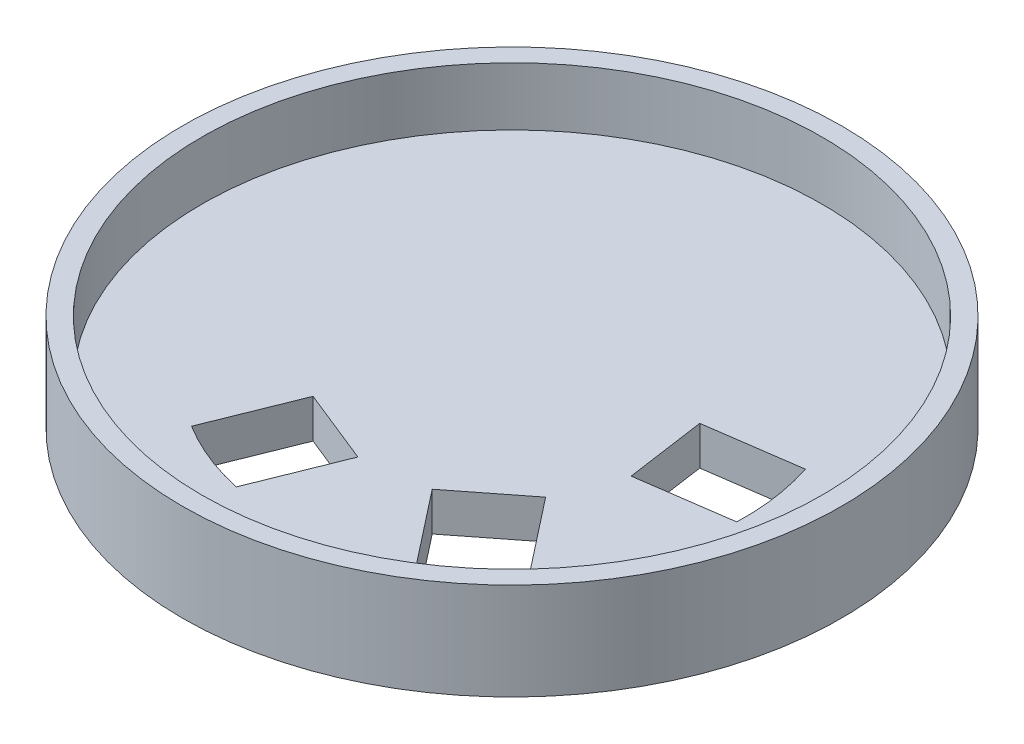
SolidWorks part; units mm, degrees
ref_plane "Front Plane" through (0, 0, 0) normal (0, 0, 1) x (1, 0, 0)
ref_plane "Top Plane" through (0, 0, 0) normal (0, 1, 0) x (1, 0, 0)
ref_plane "Right Plane" through (0, 0, 0) normal (1, 0, 0) x (0, 0, -1)
sketch "Sketch1" plane through (0, 0, 0) normal (0, 1, 0) x (1, 0, 0)
  circle A0 centre (0, 0) radius 17
  dimension "D1" = 34
extrude "Boss-Extrude1" add sketch "Sketch1" along normal blind 5
sketch "Sketch2" plane through (0, 5, 0) normal (0, 1, 0) x (1, 0, 0)
  circle A0 centre (0, 0) radius 16
  dimension "D1" = 32
extrude "Cut-Extrude1" cut sketch "Sketch2" against normal blind 3
sketch "Sketch3" plane through (0, 0, 0) normal (0, -1, 0) x (1, 0, 0)
  line L11 (-6.3426, 10.1868) -> (-4.5451, 5.717)
  line L12 (-2.476, 11.7418) -> (-0.6785, 7.272)
  line L13 (-4.5451, 5.717) -> (-0.6785, 7.272)
  line L15 (5.6508, 10.5863) -> (2.6786, 6.7947)
  line L16 (8.9307, 8.0152) -> (5.9585, 4.2236)
  line L17 (2.6786, 6.7947) -> (5.9585, 4.2236)
  line L19 (11.9934, 0.3994) -> (7.2236, 1.0776)
  line L20 (11.4067, -3.7266) -> (6.637, -3.0484)
  line L21 (7.2236, 1.0776) -> (6.637, -3.0484)
  arc A0 (-2.476, 11.7418) -> (-6.3426, 10.1868) centre (0, 0) ccw
  arc A3 (8.9307, 8.0152) -> (5.6508, 10.5863) centre (0, 0) ccw
  arc A4 (11.4067, -3.7266) -> (11.9934, 0.3994) centre (0, 0) ccw
  dimension "D1" = 7
  dimension "D2" = 3
extrude "Cut-Extrude3" cut sketch "Sketch3" against normal blind 3
